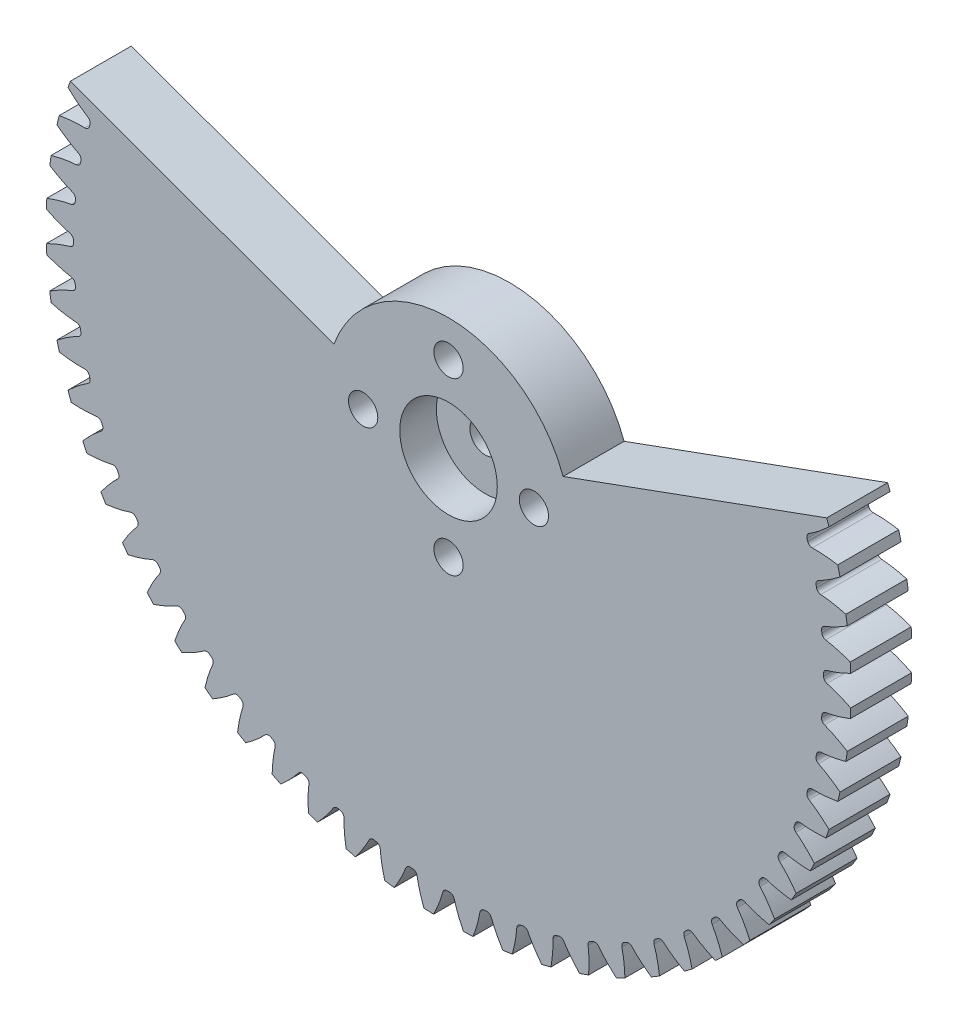
SolidWorks part; units mm, degrees
ref_plane "前视基准面" through (0, 0, 0) normal (0, 0, 1) x (1, 0, 0)
ref_plane "上视基准面" through (0, 0, 0) normal (0, 1, 0) x (1, 0, 0)
ref_plane "右视基准面" through (0, 0, 0) normal (1, 0, 0) x (0, 0, -1)
other "Configuration Table"
ref_axis "Axis1" through (0, 0, -88.99) along (0, 0, 1)
sketch "草图1" plane through (0, 0, 0) normal (0, 0, 1) x (1, 0, 0)
  circle A0 centre (0, 0) radius 33
extrude "LaShenA" add sketch "草图1" along normal blind 5
sketch "SketchA" plane through (0, 0, 5) normal (0, 0, 1) x (1, 0, 0)
  line L0 (0, 0) -> (0, 33) construction
  arc A0 (0.0966, 30.7498) -> (-0.0966, 30.7498) centre (0, 0) ccw
  arc A1 (1.5209, 33.5392) -> (-1.5209, 33.5392) centre (0, 0) ccw
  arc A2 (-0.0966, 30.7498) -> (-0.4642, 31.0289) centre (-0.0978, 31.1298) cw
  arc A3 (0.4642, 31.0289) -> (0.0966, 30.7498) centre (0.0978, 31.1298) cw
  circle A4 centre (0, 0) radius 30.0702 construction
  circle A5 centre (0, 0) radius 33 construction
  circle A6 centre (0, 0) radius 30.75 construction
  circle A7 centre (0, 0) radius 32 construction
  spline S0 degree 3 poles (0.4642, 31.0289) (0.4688, 31.0456) (0.4792, 31.0831) (0.4958, 31.142) (0.5144, 31.206) (0.5342, 31.2718) (0.555, 31.3393) (0.577, 31.4085) (0.6002, 31.4794) (0.6246, 31.552) (0.6502, 31.6262) (0.6771, 31.7021) (0.7052, 31.7796) (0.7347, 31.8588) (0.7655, 31.9395) (0.7977, 32.0219) (0.8313, 32.1058) (0.8663, 32.1912) (0.9027, 32.2782) (0.9407, 32.3667) (0.9801, 32.4567) (1.0211, 32.5482) (1.0637, 32.6411) (1.1078, 32.7355) (1.1535, 32.8313) (1.2009, 32.9285) (1.25, 33.0271) (1.3007, 33.127) (1.3532, 33.2283) (1.426, 33.3662) (1.4824, 33.4699) (1.5209, 33.5392) knots 0.096686 0.096686 0.096686 0.096686 0.113908 0.135324 0.157392 0.180114 0.203488 0.227515 0.252195 0.277528 0.303513 0.330152 0.357443 0.385386 0.413983 0.443232 0.473134 0.503689 0.534897 0.566757 0.599271 0.632437 0.666256 0.700727 0.735851 0.771629 0.808059 0.845141 0.882877 0.921265 1 1 1 1
  spline S1 degree 3 poles (-0.4642, 31.0289) (-0.4688, 31.0456) (-0.4792, 31.0831) (-0.4958, 31.142) (-0.5144, 31.206) (-0.5342, 31.2718) (-0.555, 31.3393) (-0.577, 31.4085) (-0.6002, 31.4794) (-0.6246, 31.552) (-0.6502, 31.6262) (-0.6771, 31.7021) (-0.7052, 31.7796) (-0.7347, 31.8588) (-0.7655, 31.9395) (-0.7977, 32.0219) (-0.8313, 32.1058) (-0.8663, 32.1912) (-0.9027, 32.2782) (-0.9407, 32.3667) (-0.9801, 32.4567) (-1.0211, 32.5482) (-1.0637, 32.6411) (-1.1078, 32.7355) (-1.1535, 32.8313) (-1.2009, 32.9285) (-1.25, 33.0271) (-1.3007, 33.127) (-1.3532, 33.2283) (-1.426, 33.3662) (-1.4824, 33.4699) (-1.5209, 33.5392) knots 0.096686 0.096686 0.096686 0.096686 0.113908 0.135324 0.157392 0.180114 0.203488 0.227515 0.252195 0.277528 0.303513 0.330152 0.357443 0.385386 0.413983 0.443232 0.473134 0.503689 0.534897 0.566757 0.599271 0.632437 0.666256 0.700727 0.735851 0.771629 0.808059 0.845141 0.882877 0.921265 1 1 1 1
  dimension "D1" = 0.38
  dimension "Db" = 60.1403
  dimension "Da" = 66
  dimension "Df" = 61.5
  dimension "Dn" = 64
extrude "Cut-ExtrudeA" cut sketch "SketchA" against normal blind 30
pattern_circular "www.KYTool.cn" count 64 over 360 about axis through (0, 0, -88.99) along (0, 0, 1) of "Cut-ExtrudeA"
sketch "草图4" plane through (0, 0, 5) normal (0, 0, 1) x (1, 0, 0)
  line L0 (0, 0) -> (37.3709, 0) construction
  circle A0 centre (7, 0) radius 1.2
  circle A1 centre (0, -7) radius 1.2
  circle A2 centre (-7, 0) radius 1.2
  circle A3 centre (0, 7) radius 1.2
  point P6 (0, 0)
  point P15 (0, 0)
  dimension "D1" = 2.4
  dimension "D2" = 7
  dimension "D3" = 4
extrude "切除-拉伸2" cut sketch "草图4" against normal blind 10
sketch "草图5" plane through (0, 0, 5) normal (0, 0, 1) x (1, 0, 0)
  circle A0 centre (0, 0) radius 4
  point P3 (0, 0)
  dimension "D1" = 8
extrude "切除-拉伸3" cut sketch "草图5" against normal blind 3
sketch "草图6" plane through (0, 0, 2) normal (0, 0, 1) x (1, 0, 0)
  circle A0 centre (0, 0) radius 1.25
  dimension "D1" = 2.5
extrude "切除-拉伸4" cut sketch "草图6" against normal blind 3
sketch "草图7" plane through (0, 0, 5) normal (0, 0, 1) x (1, 0, 0)
  line L0 (-1000, 0) -> (-10, 0) construction
  line L1 (9.3969, 3.4202) -> (40.2372, 14.6451)
  line L2 (-9.3969, 3.4202) -> (-39.9308, 14.5336)
  line L3 (-39.9308, 14.5336) -> (-1.0911, 49.2823)
  line L4 (-1.0911, 49.2823) -> (40.2372, 14.6451)
  line L5 (10, 0) -> (37.7346, 0) construction
  arc A0 (9.3969, 3.4202) -> (-9.3969, 3.4202) centre (0, 0) ccw
  dimension "D3" = 20
  dimension "D1" = 20
  dimension "D2" = 20
extrude "切除-拉伸5" cut sketch "草图7" against normal blind 13
sketch "草图8" plane through (0, 0, 5) normal (0, 0, 1) x (1, 0, 0)
  circle A0 centre (0, 0) radius 32 construction
  dimension "D1" = 64
